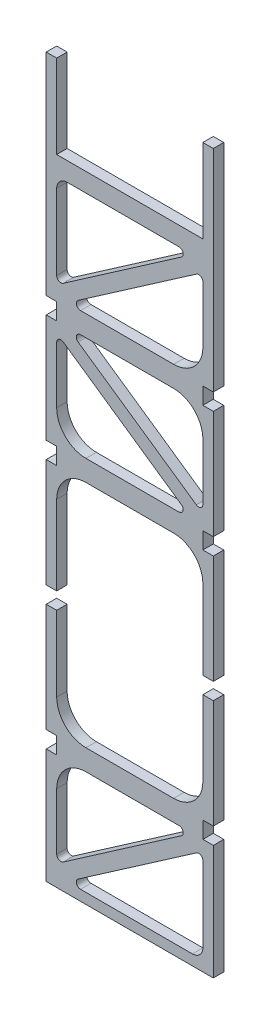
SolidWorks part; units mm, degrees
material "Balsa"
ref_plane "Front Plane" through (0, 0, 0) normal (0, 0, 1) x (1, 0, 0)
ref_plane "Top Plane" through (0, 0, 0) normal (0, 1, 0) x (1, 0, 0)
ref_plane "Right Plane" through (0, 0, 0) normal (1, 0, 0) x (0, 0, -1)
sketch "Model" plane through (0, 0, 0) normal (0, 0, 1) x (1, 0, 0)
  line L0 (-80.7688, 311.15) -> (-24.13, 311.15)
  line L1 (-10.3358, 365.5406) -> (-82.2146, 315.7784)
  line L2 (-6.35, 328.93) -> (-6.35, 363.4522)
  line L3 (-95.25, 287.2522) -> (-95.25, 252.73)
  line L4 (-19.3854, 239.5784) -> (-91.2642, 289.3406)
  line L5 (-77.47, 234.95) -> (-20.8312, 234.95)
  line L6 (-80.7688, 158.75) -> (-12.7, 158.75)
  line L7 (-10.3358, 213.1406) -> (-82.2146, 163.3784)
  line L8 (-6.35, 165.1) -> (-6.35, 211.0522)
  line L9 (-20.8312, 222.25) -> (-88.9, 222.25)
  line L10 (-91.2642, 167.8594) -> (-19.3854, 217.6216)
  line L11 (-95.25, 215.9) -> (-95.25, 169.9478)
  line L12 (-82.2146, 293.8216) -> (-10.3358, 244.0594)
  line L13 (-24.13, 298.45) -> (-80.7688, 298.45)
  line L14 (-6.35, 246.1478) -> (-6.35, 280.67)
  line L15 (-95.25, 134.8522) -> (-95.25, 88.9)
  line L16 (-19.3854, 87.1784) -> (-91.2642, 136.9406)
  line L17 (-88.9, 82.55) -> (-20.8312, 82.55)
  line L18 (-80.7688, 6.35) -> (-12.7, 6.35)
  line L19 (-10.3358, 60.7406) -> (-82.2146, 10.9784)
  line L20 (-6.35, 12.7) -> (-6.35, 58.6522)
  line L21 (-20.8312, 69.85) -> (-77.47, 69.85)
  line L22 (-91.2642, 15.4594) -> (-19.3854, 65.2216)
  line L23 (-95.25, 52.07) -> (-95.25, 17.5478)
  line L24 (-20.8312, 374.65) -> (-88.9, 374.65)
  line L25 (-91.2642, 320.2594) -> (-19.3854, 370.0216)
  line L26 (-95.25, 368.3) -> (-95.25, 322.3478)
  line L27 (-82.2146, 141.4216) -> (-10.3358, 91.6594)
  line L28 (-12.7, 146.05) -> (-80.7688, 146.05)
  line L29 (-6.35, 93.7478) -> (-6.35, 139.7)
  line L30 (-95.25, 386.08) -> (-6.35, 386.08)
  line L31 (-95.25, 386.08) -> (-95.25, 436.88)
  line L32 (-101.6, 436.88) -> (-95.25, 436.88)
  line L33 (-101.6, 0) -> (-101.6, 436.88)
  line L34 (-101.6, 0) -> (0, 0)
  line L35 (0, 0) -> (0, 436.88)
  line L36 (-6.35, 436.88) -> (0, 436.88)
  line L37 (-6.35, 386.08) -> (-6.35, 436.88)
  arc A0 (-77.47, 69.85) -> (-95.25, 52.07) centre (-77.47, 52.07) ccw
  arc A1 (-82.2146, 315.7784) -> (-80.7688, 311.15) centre (-80.7688, 313.69) ccw
  arc A2 (-6.35, 363.4522) -> (-10.3358, 365.5406) centre (-8.89, 363.4522) ccw
  arc A3 (-6.35, 328.93) -> (-24.13, 311.15) centre (-24.13, 328.93) cw
  arc A4 (-91.2642, 289.3406) -> (-95.25, 287.2522) centre (-92.71, 287.2522) ccw
  arc A5 (-20.8312, 234.95) -> (-19.3854, 239.5784) centre (-20.8312, 237.49) ccw
  arc A6 (-12.7, 158.75) -> (-6.35, 165.1) centre (-12.7, 165.1) ccw
  arc A7 (-82.2146, 163.3784) -> (-80.7688, 158.75) centre (-80.7688, 161.29) ccw
  arc A8 (-6.35, 211.0522) -> (-10.3358, 213.1406) centre (-8.89, 211.0522) ccw
  arc A9 (-88.9, 222.25) -> (-95.25, 215.9) centre (-88.9, 215.9) ccw
  arc A10 (-19.3854, 217.6216) -> (-20.8312, 222.25) centre (-20.8312, 219.71) ccw
  arc A11 (-95.25, 169.9478) -> (-91.2642, 167.8594) centre (-92.71, 169.9478) ccw
  arc A12 (-10.3358, 244.0594) -> (-6.35, 246.1478) centre (-8.89, 246.1478) ccw
  arc A13 (-80.7688, 298.45) -> (-82.2146, 293.8216) centre (-80.7688, 295.91) ccw
  arc A14 (-6.35, 280.67) -> (-24.13, 298.45) centre (-24.13, 280.67) ccw
  arc A15 (-95.25, 88.9) -> (-88.9, 82.55) centre (-88.9, 88.9) ccw
  arc A16 (-91.2642, 136.9406) -> (-95.25, 134.8522) centre (-92.71, 134.8522) ccw
  arc A17 (-20.8312, 82.55) -> (-19.3854, 87.1784) centre (-20.8312, 85.09) ccw
  arc A18 (-12.7, 6.35) -> (-6.35, 12.7) centre (-12.7, 12.7) ccw
  arc A19 (-82.2146, 10.9784) -> (-80.7688, 6.35) centre (-80.7688, 8.89) ccw
  arc A20 (-6.35, 58.6522) -> (-10.3358, 60.7406) centre (-8.89, 58.6522) ccw
  arc A21 (-77.47, 234.95) -> (-95.25, 252.73) centre (-77.47, 252.73) cw
  arc A22 (-19.3854, 65.2216) -> (-20.8312, 69.85) centre (-20.8312, 67.31) ccw
  arc A23 (-95.25, 17.5478) -> (-91.2642, 15.4594) centre (-92.71, 17.5478) ccw
  arc A24 (-88.9, 374.65) -> (-95.25, 368.3) centre (-88.9, 368.3) ccw
  arc A25 (-19.3854, 370.0216) -> (-20.8312, 374.65) centre (-20.8312, 372.11) ccw
  arc A26 (-95.25, 322.3478) -> (-91.2642, 320.2594) centre (-92.71, 322.3478) ccw
  arc A27 (-10.3358, 91.6594) -> (-6.35, 93.7478) centre (-8.89, 93.7478) ccw
  arc A28 (-80.7688, 146.05) -> (-82.2146, 141.4216) centre (-80.7688, 143.51) ccw
  arc A29 (-6.35, 139.7) -> (-12.7, 146.05) centre (-12.7, 139.7) ccw
  point P0 (-6.35, 312.3955)
  point P9 (-95.25, 234.95)
  point P63 (-95.25, 69.85)
  point P64 (-93.8853, 234.95)
  point P98 (-92.71, 69.85)
  dimension "D1" = 17.78
  dimension "D2" = 17.78
extrude "Boss-Extrude1" add sketch "Model" along normal blind 6.35 contours L37 L30 L31 L32 L33 L34 L35 L36 A29 L29 A27 L27 A28 L28 A26 L26 A24 L24 A25 L25 A23 L23 L21 A22 L22 A20 L20 A18 L18 A19 L19 A17 L17 A15 L15 A16 L16 L14 A12 L12 A13 L13 | L11 A11 L10 A10 L9 A9 | L8 A8 L7 A7 L6 A6 | L29 A29 L28 A28 L27 A27 | L17 A17 L16 A16 L15 A15 region at (-33.751, 177.8784, 0) region at (-67.849, 203.1216, 0) region at (-67.849, 101.6784, 0) region at (-33.751, 126.9216, 0) region at (-50.8, 381.5946, 0)
sketch "Sketch1" plane through (0, 0, 6.35) normal (0, 0, 1) x (1, 0, 0)
  line L0 (-95.25, 215.9) -> (-95.25, 169.9478) construction
  line L1 (-24.13, 82.55) -> (-77.47, 82.55)
  line L2 (-6.35, 100.33) -> (-6.35, 204.47)
  line L3 (-24.13, 222.25) -> (-77.47, 222.25)
  line L4 (-95.25, 100.33) -> (-95.25, 204.47)
  line L5 (-20.8312, 222.25) -> (-88.9, 222.25) construction
  line L6 (-88.9, 82.55) -> (-20.8312, 82.55) construction
  arc A0 (-77.47, 82.55) -> (-95.25, 100.33) centre (-77.47, 100.33) cw
  arc A1 (-77.47, 222.25) -> (-95.25, 204.47) centre (-77.47, 204.47) ccw
  arc A2 (-6.35, 204.47) -> (-24.13, 222.25) centre (-24.13, 204.47) ccw
  arc A3 (-24.13, 82.55) -> (-6.35, 100.33) centre (-24.13, 100.33) ccw
  point P14 (-95.25, 222.25)
  point P17 (-6.35, 222.25)
  dimension "D2" = 17.78
  dimension "D1" = 88.9
extrude "Cut-Extrude1" cut sketch "Sketch1" along direction (0, 0, 1) on the side against the normal up to surface (6.35 mm away) contours L1 A3 L2 A2 L3 A1 L4 A0 | A3 L1 A0 L4 A1 L3 A2 L2 region at (-50.8, 152.4, 6.35) up to face at (-68.521, 355.145, 0)
sketch "Sketch2" plane through (0, 0, 6.35) normal (0, 0, 1) x (1, 0, 0)
  line L0 (-101.6, 298.45) -> (0, 298.45)
  line L1 (-95.25, 63.5) -> (-95.25, 17.5478) construction
  line L2 (-101.6, 436.88) -> (-101.6, 0) construction
  line L3 (0, 0) -> (0, 436.88) construction
  line L4 (-101.6, 222.25) -> (0, 222.25)
  line L5 (-101.6, 80.01) -> (-95.25, 80.01)
  line L6 (-12.7, 298.45) -> (-80.7688, 298.45) construction
  line L7 (-101.6, 308.61) -> (-95.25, 308.61)
  line L8 (-101.6, 308.61) -> (-101.6, 298.45)
  line L9 (-101.6, 298.45) -> (-95.25, 298.45)
  line L10 (-95.25, 308.61) -> (-95.25, 298.45)
  line L11 (-101.6, 232.41) -> (-95.25, 232.41)
  line L12 (-101.6, 232.41) -> (-101.6, 222.25)
  line L13 (-101.6, 222.25) -> (-95.25, 222.25)
  line L14 (-95.25, 232.41) -> (-95.25, 222.25)
  line L15 (-20.8312, 222.25) -> (-88.9, 222.25) construction
  line L16 (-95.25, 215.9) -> (-95.25, 88.9) construction
  line L17 (-101.6, 156.21) -> (-95.25, 156.21)
  line L18 (-101.6, 156.21) -> (-101.6, 146.05)
  line L19 (-101.6, 146.05) -> (-95.25, 146.05)
  line L20 (-95.25, 156.21) -> (-95.25, 146.05)
  line L21 (-101.6, 80.01) -> (-101.6, 69.85)
  line L22 (-101.6, 69.85) -> (-95.25, 69.85)
  line L23 (-95.25, 80.01) -> (-95.25, 69.85)
  line L24 (-50.8, 0) -> (-50.8, 386.08) construction
  line L25 (-101.6, 0) -> (0, 0) construction
  line L26 (-6.35, 386.08) -> (-95.25, 386.08) construction
  line L27 (0, 69.85) -> (-6.35, 69.85)
  line L28 (-6.35, 80.01) -> (-6.35, 69.85)
  line L29 (0, 80.01) -> (-6.35, 80.01)
  line L30 (0, 80.01) -> (0, 69.85)
  line L31 (0, 146.05) -> (-6.35, 146.05)
  line L32 (-6.35, 156.21) -> (-6.35, 146.05)
  line L33 (0, 156.21) -> (-6.35, 156.21)
  line L34 (0, 156.21) -> (0, 146.05)
  line L35 (0, 222.25) -> (-6.35, 222.25)
  line L36 (-6.35, 232.41) -> (-6.35, 222.25)
  line L37 (0, 232.41) -> (-6.35, 232.41)
  line L38 (0, 232.41) -> (0, 222.25)
  line L39 (0, 298.45) -> (-6.35, 298.45)
  line L40 (-6.35, 308.61) -> (-6.35, 298.45)
  line L41 (0, 308.61) -> (-6.35, 308.61)
  line L42 (0, 308.61) -> (0, 298.45)
  dimension "D1" = 6.35
  dimension "D2" = 10.16
  dimension "D3" = 10.16
  dimension "D4" = 66.04
  dimension "D5" = 10.16
  dimension "D6" = 10.16
  dimension "D7" = 66.04
extrude "Cut-Extrude2" cut sketch "Sketch2" against normal up to surface (6.35 mm away) contours L14 L11 L12 L4 | L10 L7 L8 L0 | L30 L29 L28 L27 | L34 L33 L32 L31 | L42 L41 L40 L0 | L38 L37 L36 L4 | L20 L17 L18 L19 | L23 L5 L21 L22 | L21 L5 L23 L22 region at (-98.425, 303.53, 6.35) region at (-3.175, 303.53, 6.35) region at (-98.425, 227.33, 6.35) region at (-3.175, 227.33, 6.35) region at (-98.425, 74.93, 6.35) region at (-98.425, 151.13, 6.35) region at (-3.175, 74.93, 6.35) region at (-3.175, 151.13, 6.35) up to face at (-50.8, 152.4, 0)
equation "\"thick\"=0.25"
equation "\"D1@Boss-Extrude1\"=\"thick\""
